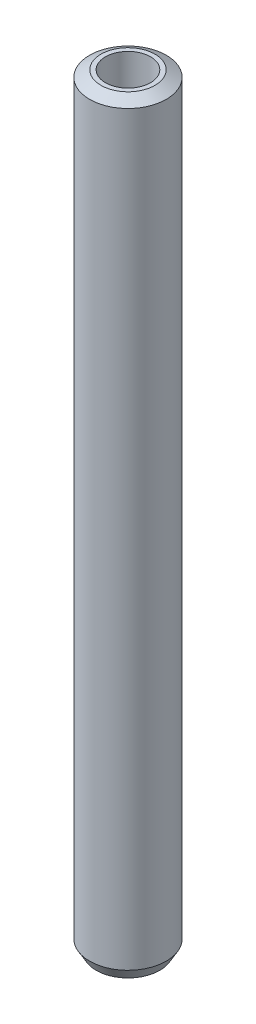
SolidWorks part; units mm, degrees
ref_plane "Front Plane" through (0, 0, 0) normal (0, 0, 1) x (1, 0, 0)
ref_plane "Top Plane" through (0, 0, 0) normal (0, 1, 0) x (1, 0, 0)
ref_plane "Right Plane" through (0, 0, 0) normal (1, 0, 0) x (0, 0, -1)
sketch "Sketch1" plane through (0, 0, 0) normal (0, 1, 0) x (1, 0, 0)
  circle A0 centre (0, 0) radius 30
  dimension "SHAFT_OD" = 60
extrude "Boss-Extrude1" add sketch "Sketch1" along normal blind 598.4882
sketch "Sketch2" plane through (0, 0, 0) normal (0, 1, 0) x (1, 0, 0)
  circle A0 centre (0, 0) radius 17.6414
  dimension "BORE_D" = 35.2827
extrude "Cut-Extrude1" cut sketch "Sketch2" along normal through all
chamfer "Chamfer1" distance 5.1002 angle 60 2 edges at (0, 598.4882, 30) (0, 0, 30) first distance on face at (0, 598.4882, 30) first distance on face at (0, 0, 17.6414)
